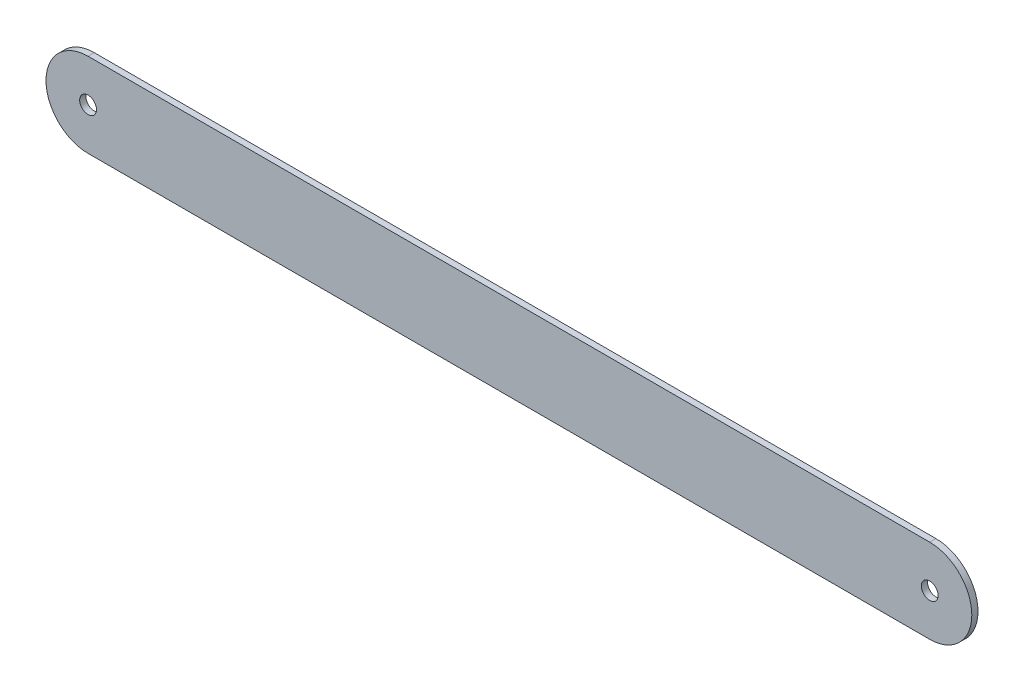
SolidWorks part; units mm, degrees
ref_plane "Front Plane" through (0, 0, 0) normal (0, 0, 1) x (1, 0, 0)
ref_plane "Top Plane" through (0, 0, 0) normal (0, 1, 0) x (1, 0, 0)
ref_plane "Right Plane" through (0, 0, 0) normal (1, 0, 0) x (0, 0, -1)
sketch "Sketch1" plane through (0, 0, 0) normal (0, 0, 1) x (1, 0, 0)
  line L0 (-28.3445, 0) -> (71.6555, 0) construction
  line L1 (-28.3445, 5) -> (71.6555, 5)
  line L2 (-28.3445, -5) -> (71.6555, -5)
  arc A0 (-28.3445, 5) -> (-28.3445, -5) centre (-28.3445, 0) ccw
  arc A1 (71.6555, -5) -> (71.6555, 5) centre (71.6555, 0) ccw
  circle A2 centre (-28.3445, 0) radius 1
  circle A3 centre (71.6555, 0) radius 1
  point P3 (21.6555, 0)
  dimension "D1" = 100
  dimension "D2" = 10
base flange "Base-Flange1" sketch "Sketch1" thickness 0.7366 reverse thickness direction no parameters "D1"=0.7366
sketch "Bend-Lines1" plane through (0, 0, 0) normal (0, 1, 0) x (1, 0, 0)
sketch "Bounding-Box1" plane through (0, 0, 0) normal (0, 1, 0) x (1, 0, 0)
sheet metal parameters "Sheet-Metal1" thickness 0.7366 parameters "D1"=0.7366
flat pattern "Flat-Pattern1" [suppressed]
sketch "Bend-Lines2" plane through (0, 0, 0) normal (0, 1, 0) x (1, 0, 0)
sketch "Bounding-Box2" [suppressed] plane through (0, 0, 0) normal (0, 1, 0) x (1, 0, 0)
